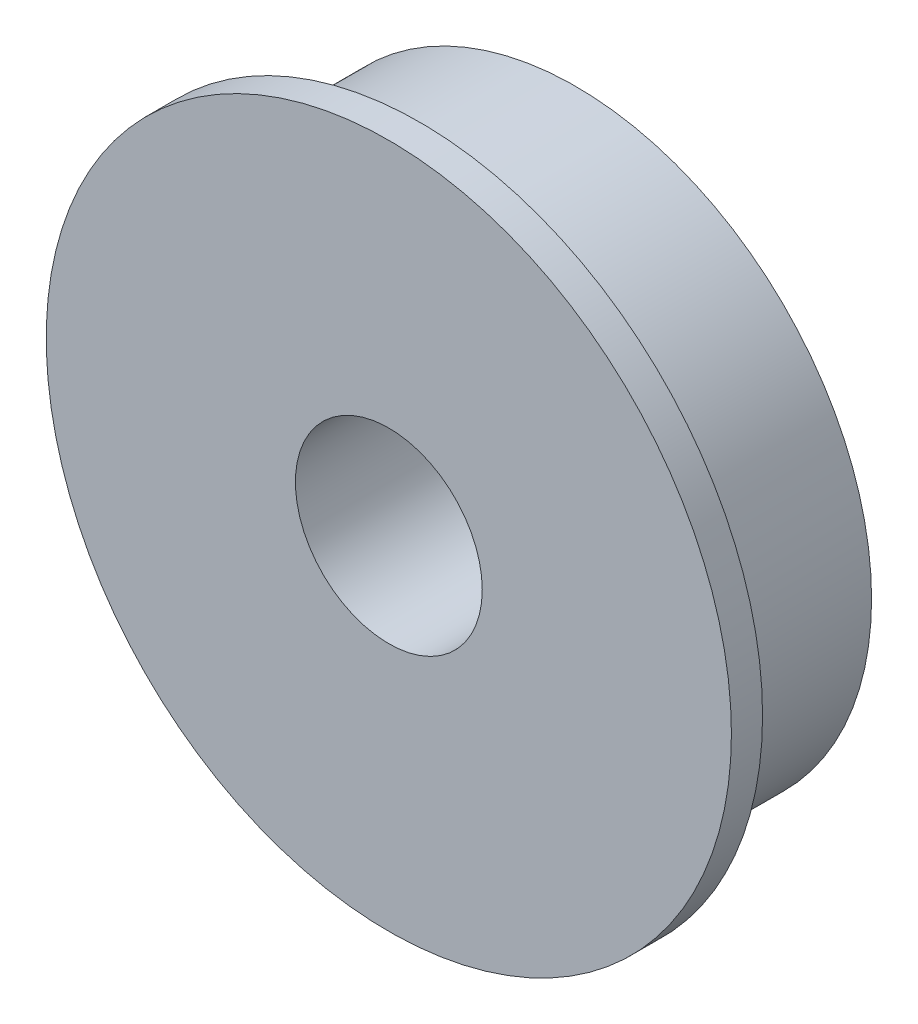
SolidWorks part; units mm, degrees
ref_plane "Płaszczyzna przednia" through (0, 0, 0) normal (0, 0, 1) x (1, 0, 0)
ref_plane "Płaszczyzna górna" through (0, 0, 0) normal (0, 1, 0) x (1, 0, 0)
ref_plane "Płaszczyzna prawa" through (0, 0, 0) normal (1, 0, 0) x (0, 0, -1)
sketch "Szkic1" plane through (0, 0, 0) normal (0, 0, 1) x (1, 0, 0)
  circle A0 centre (0, 0) radius 3
  circle A1 centre (0, 0) radius 9.5
  dimension "D1" = 19
  dimension "D2" = 6
extrude "Dodanie-wyciągnięcie1" add sketch "Szkic1" along normal blind 6
sketch "Szkic2" plane through (0, 0, 6) normal (0, 0, 1) x (1, 0, 0)
  circle A0 centre (0, 0) radius 9.5
  circle A1 centre (0, 0) radius 11
  dimension "D1" = 19
  dimension "D2" = 22
extrude "Dodanie-wyciągnięcie2" add sketch "Szkic2" against normal blind 1
